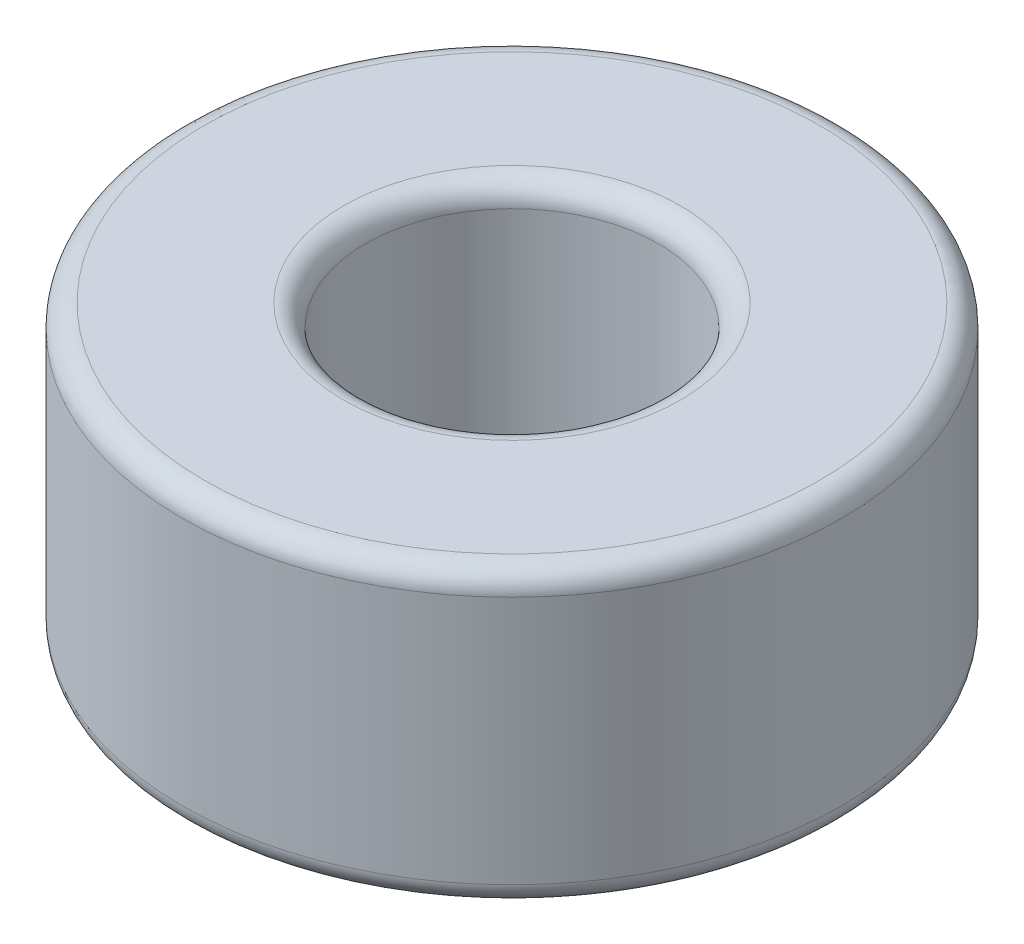
SolidWorks part; units mm, degrees
ref_plane "Спереди" through (0, 0, 0) normal (0, 0, 1) x (1, 0, 0)
ref_plane "Сверху" through (0, 0, 0) normal (0, 1, 0) x (1, 0, 0)
ref_plane "Справа" through (0, 0, 0) normal (1, 0, 0) x (0, 0, -1)
sketch "Эскиз1" plane through (0, 0, 0) normal (0, 1, 0) x (1, 0, 0)
  circle A0 centre (0, 0) radius 2
  circle A1 centre (0, 0) radius 4.5
  dimension "D1" = 4
  dimension "D2" = 9
extrude "Бобышка-Вытянуть1" add sketch "Эскиз1" along normal blind 4
fillet "Скругление1" radius 0.3 4 edges at (0, 0, 2) (0, 0, 4.5) (0, 4, 2) (0, 4, 4.5)
